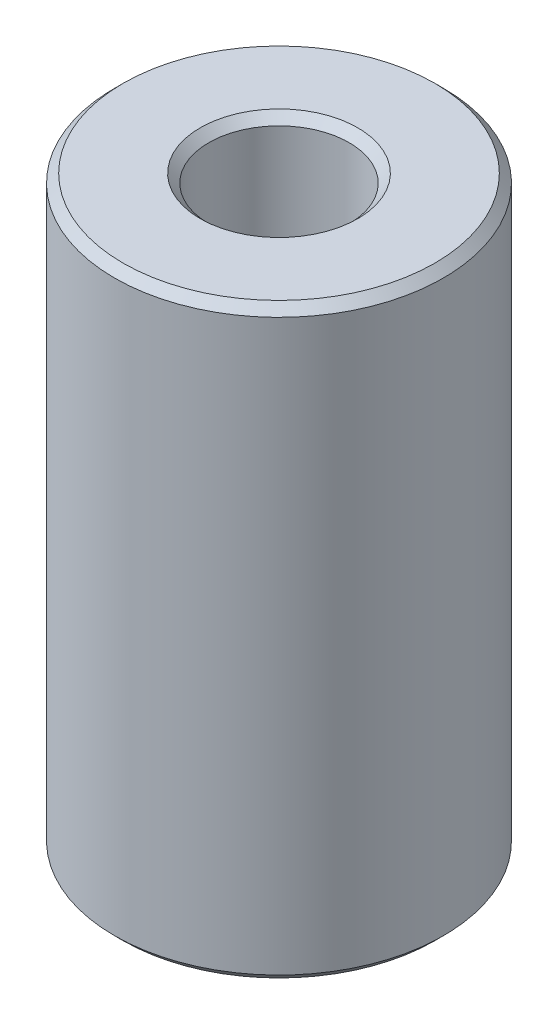
SolidWorks part; units mm, degrees
ref_plane "Front Plane" through (0, 0, 0) normal (0, 0, 1) x (1, 0, 0)
ref_plane "Top Plane" through (0, 0, 0) normal (0, 1, 0) x (1, 0, 0)
ref_plane "Right Plane" through (0, 0, 0) normal (1, 0, 0) x (0, 0, -1)
sketch "Sketch1" plane through (0, 0, 0) normal (0, 1, 0) x (1, 0, 0)
  circle A0 centre (0, 0) radius 32.5
  dimension "SLEEVE_OD" = 65
extrude "Boss-Extrude1" add sketch "Sketch1" along normal blind 115.995
sketch "Sketch2" plane through (0, 0, 0) normal (0, 1, 0) x (1, 0, 0)
  circle A0 centre (0, 0) radius 13.876
  dimension "BORE_D" = 27.7521
extrude "Cut-Extrude1" cut sketch "Sketch2" along normal through all
chamfer "Chamfer1" distance 1.6974 angle 45 4 edges at (0, 115.995, 13.876) (0, 0, 13.876) (0, 0, 32.5) (0, 115.995, 32.5)
